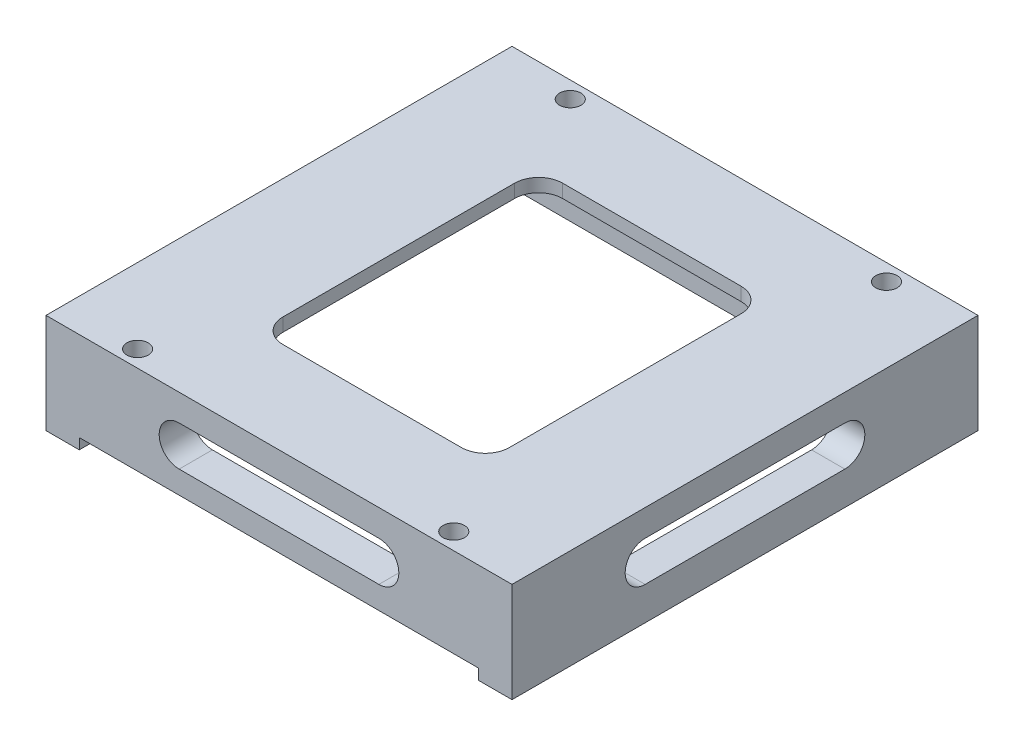
SolidWorks part; units mm, degrees
ref_plane "Front Plane" through (0, 0, 0) normal (0, 0, 1) x (1, 0, 0)
ref_plane "Top Plane" through (0, 0, 0) normal (0, 1, 0) x (1, 0, 0)
ref_plane "Right Plane" through (0, 0, 0) normal (1, 0, 0) x (0, 0, -1)
sketch "Sketch1" plane through (0, 0, 0) normal (0, 1, 0) x (1, 0, 0)
  line L0 (-30, -30) -> (-30, 30)
  line L1 (-35, -35) -> (35, -35)
  line L2 (-35, -35) -> (-35, 35)
  line L3 (-35, 35) -> (35, 35)
  line L4 (35, -35) -> (35, 35)
  line L5 (-35, -35) -> (35, 35) construction
  line L6 (-35, 35) -> (35, -35) construction
  line L7 (-30, 30) -> (30, 30)
  line L8 (30, -30) -> (30, 30)
  line L9 (-30, -30) -> (30, -30)
  point P0 (0, 0)
  dimension "D1" = 70
  dimension "D2" = 70
  dimension "D3" = 5
extrude "Boss-Extrude1" add sketch "Sketch1" along normal blind 15
extrude "Boss-Extrude2" add sketch "Sketch1<2>" against normal blind 2 from surface contours L1 L4 L3 L2 starting at face at (0, 15, 0)
sketch "Sketch1<2>" plane through (0, 0, 0) normal (0, 1, 0) x (1, 0, 0) same geometry as "Sketch1"
sketch "Sketch2" plane through (0, 0, 0) normal (0, 0, 1) x (1, 0, 0)
  line L0 (-15, 8) -> (15, 8) construction
  line L1 (-15, 11) -> (15, 11)
  line L2 (-15, 5) -> (15, 5)
  arc A0 (-15, 11) -> (-15, 5) centre (-15, 8) ccw
  arc A1 (15, 5) -> (15, 11) centre (15, 8) ccw
  point P2 (0, 8)
  dimension "D3" = 3
  dimension "D1" = 30
  dimension "D2" = 8
extrude "Cut-Extrude1" cut sketch "Sketch2" against normal mid plane 107 contours L2 A1 L1 A0
sketch "Sketch3" plane through (0, 0, 0) normal (1, 0, 0) x (0, 0, -1)
  line L0 (15, 8) -> (-15, 8) construction
  line L1 (15, 5) -> (-15, 5)
  line L2 (15, 11) -> (-15, 11)
  arc A0 (15, 5) -> (15, 11) centre (15, 8) ccw
  arc A1 (-15, 11) -> (-15, 5) centre (-15, 8) ccw
  point P2 (0, 8)
  dimension "D2" = 3
  dimension "D1" = 30
  dimension "D3" = 8
extrude "Cut-Extrude2" cut sketch "Sketch3" against normal mid plane 77
sketch "Sketch4" plane through (0, 0, 0) normal (0, 1, 0) x (1, 0, 0)
  line L0 (35, -35) -> (35, 35) construction
  line L1 (35, 35) -> (-35, 35) construction
  line L18 (17, -21) -> (17, 21)
  line L19 (17, 21) -> (-17, 21)
  line L20 (-17, 21) -> (-17, -21)
  line L21 (-17, -21) -> (17, -21)
  dimension "D3" = 34
  dimension "D1" = 18
  dimension "D2" = 14
  dimension "D4" = 42
extrude "Cut-Extrude3" cut sketch "Sketch4" along normal blind 5 from surface contours L20 L21 L18 L19 region at (0, 0, 0) starting at face at (0, 13, 0)
fillet "Fillet1" radius 3.6 4 edges at (17, 14, 21) (-17, 14, 21) (17, 14, -21) (-17, 14, -21)
sketch "Sketch5" plane through (0, 0, 0) normal (0, 1, 0) x (1, 0, 0)
  line L0 (-35, 35) -> (-35, -35) construction
  line L1 (23.75, 32.5) -> (-23.75, 32.5) construction
  line L2 (23.75, 32.5) -> (23.75, -32.5) construction
  line L3 (23.75, -32.5) -> (-23.75, -32.5) construction
  line L4 (-23.75, 32.5) -> (-23.75, -32.5) construction
  line L5 (23.75, 32.5) -> (-23.75, -32.5) construction
  line L6 (23.75, -32.5) -> (-23.75, 32.5) construction
  circle A0 centre (-23.75, 32.5) radius 1.6
  circle A1 centre (-23.75, -32.5) radius 1.6
  circle A2 centre (23.75, 32.5) radius 1.6
  circle A3 centre (23.75, -32.5) radius 1.6
  point P1 (0, 0)
  dimension "D3" = 3.2
  dimension "D1" = 65
  dimension "D2" = 11.25
extrude "Cut-Extrude4" cut sketch "Sketch5" along normal blind 25
sketch "Sketch7" plane through (0, 0, 0) normal (0, 1, 0) x (1, 0, 0)
  line L0 (30, 30) -> (-30, 30) construction
  line L1 (30, 35) -> (-30, 35)
  line L2 (30, 35) -> (30, 30)
  line L3 (30, 30) -> (-30, 30)
  line L4 (-30, 35) -> (-30, 30)
  line L5 (30, 35) -> (-30, 30) construction
  line L6 (30, 30) -> (-30, 35) construction
  line L7 (-30, -30) -> (30, -30) construction
  line L14 (30, -35) -> (-30, -35)
  line L15 (30, -35) -> (30, -30)
  line L16 (30, -30) -> (-30, -30)
  line L17 (-30, -35) -> (-30, -30)
  line L18 (30, -35) -> (-30, -30) construction
  line L19 (30, -30) -> (-30, -35) construction
  point P0 (0, 32.5)
  point P7 (0, 0)
  point P13 (0, -32.5)
  point P20 (0, 0)
  dimension "D1" = 5
  dimension "D2" = 60
extrude "Cut-Extrude5" cut sketch "Sketch7" along normal blind 1.6
